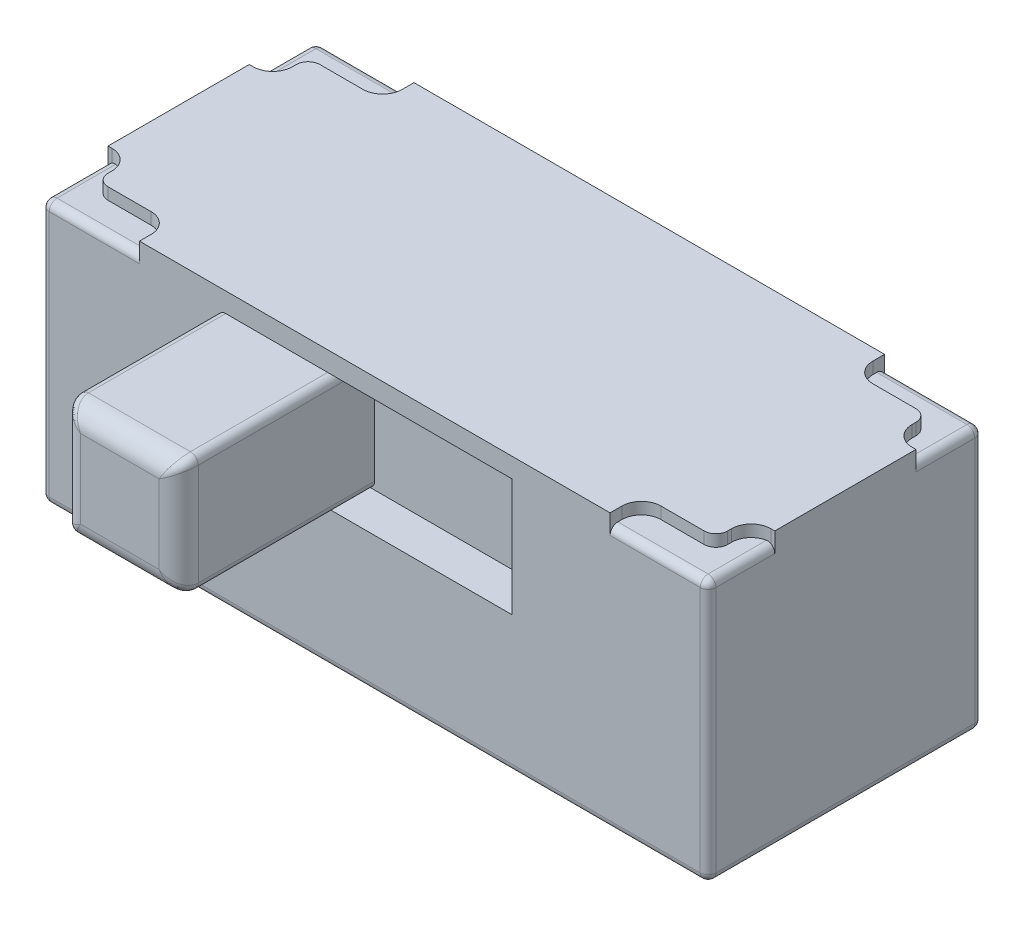
SolidWorks part; units mm, degrees
ref_plane "Front Plane" through (0, 0, 0) normal (0, 0, 1) x (1, 0, 0)
ref_plane "Top Plane" through (0, 0, 0) normal (0, 1, 0) x (1, 0, 0)
ref_plane "Right Plane" through (0, 0, 0) normal (1, 0, 0) x (0, 0, -1)
sketch "Sketch1" plane through (0, 0, 0) normal (0, 1, 0) x (1, 0, 0)
  line L1 (-4.25, -1.75) -> (4.25, -1.75)
  line L2 (-4.25, -1.75) -> (-4.25, 1.75)
  line L3 (-4.25, 1.75) -> (4.25, 1.75)
  line L4 (4.25, -1.75) -> (4.25, 1.75)
  line L5 (-4.25, -1.75) -> (4.25, 1.75) construction
  line L6 (-4.25, 1.75) -> (4.25, -1.75) construction
  point P0 (0, 0)
  dimension "D1" = 8.5
  dimension "D2" = 3.5
extrude "Bloc" add sketch "Sketch1" along normal blind 3.5
sketch "Sketch2" plane through (0, 0, 0) normal (1, 0, 0) x (0, 0, -1)
  line L0 (-2.1, 0) -> (-2.5, 0)
  line L1 (-1.75, 3.5) -> (-1.75, 0) construction
  line L2 (-1.75, 0.35) -> (-1.75, 0.75)
  line L3 (-1.75, 0) -> (1.75, 0) construction
  arc A0 (-1.75, 0.35) -> (-2.1, 0) centre (-2.1, 0.35) cw
  dimension "D1" = 0.4
  dimension "D2" = 2.5
extrude "Patte" add sketch "Sketch2" along normal mid plane 0.6 separate body thin thin type one direction reverse wall 0.25
pattern_linear "LPattern1" count 2 spacing 2.5 along (1, 0, 0) count 2 spacing 2.5 along (-1, 0, 0) of "Patte" pattern seed only yes
mirror "Mirror1" about plane through (0, 0, 0) normal (0, 0, 1) of "LPattern1", "Patte"
sketch "Sketch4" plane through (0, 0, 1.75) normal (0, 0, 1) x (1, 0, 0)
  line L0 (-1.75, 2.5) -> (1.75, 2.5) construction
  line L1 (-1.75, 3.25) -> (1.75, 3.25)
  line L2 (-1.75, 3.25) -> (-1.75, 1.75)
  line L3 (-1.75, 1.75) -> (1.75, 1.75)
  line L4 (1.75, 3.25) -> (1.75, 1.75)
  line L5 (-4.25, 0) -> (4.25, 0) construction
  line L6 (0, 3.25) -> (0, 1.75) construction
  line L7 (0, 1.75) -> (0, 0) construction
  line L8 (0.3, 0) -> (-0.3, 0) construction
  dimension "D1" = 2.5
  dimension "D2" = 3.5
  dimension "D3" = 1.5
extrude "Découpe switch" cut sketch "Sketch4" against normal blind 0.5
sketch "Sketch3" plane through (0, 0, 1.25) normal (0, 0, 1) x (1, 0, 0)
  line L0 (-4.25, 3.5) -> (4.25, 3.5) construction
  line L1 (-2, 3.25) -> (-0.5, 3.25)
  line L2 (-2, 3.25) -> (-2, 1.75)
  line L3 (-2, 1.75) -> (-0.5, 1.75)
  line L4 (-0.5, 3.25) -> (-0.5, 1.75)
  line L5 (0, 3.5) -> (0, 0) construction
  line L6 (-1.25, 1.75) -> (-1.25, 3.25) construction
  line L7 (-1.25, 2.5) -> (1.25, 2.5) construction
  line L8 (1.25, 3.5) -> (1.25, 0) construction
  line L9 (-4.25, 0) -> (4.25, 0) construction
  line L10 (-2, 2.5) -> (-0.5, 2.5) construction
  point P19 (0, 2.5)
  dimension "D1" = 1.5
  dimension "D2" = 1.5
  dimension "D3" = 2.5
  dimension "D4" = 2.5
extrude "Switch" add sketch "Sketch3" along normal offset from surface (2.5 mm away) 2 separate body up to face at (0, 2.5, 1.75) offset beyond the face yes
sketch "Sketch5" plane through (0, 3.5, 0) normal (0, 1, 0) x (1, 0, 0)
  line L0 (-4.25, 1.75) -> (-3, 1.75)
  line L1 (4.25, 1.75) -> (-4.25, 1.75) construction
  line L2 (-3, 1.75) -> (-3, 1.6)
  line L3 (-3.25, 1.35) -> (-3.8, 1.35)
  line L4 (-3.95, 1.2) -> (-3.95, 1.15)
  line L5 (-4.2, 0.9) -> (-4.25, 0.9)
  line L6 (-4.25, 1.75) -> (-4.25, -1.75) construction
  line L7 (-4.25, 0.9) -> (-4.25, 1.75)
  line L8 (-4.25, 0) -> (4.25, 0) construction
  line L9 (4.25, -1.75) -> (4.25, 1.75) construction
  line L10 (4.25, 0.9) -> (4.25, 1.75)
  line L11 (0.3, 1.75) -> (-0.3, 1.75) construction
  line L12 (0, 1.75) -> (0, -1.75) construction
  line L13 (-4.25, -1.75) -> (4.25, -1.75) construction
  line L14 (4.2, 0.9) -> (4.25, 0.9)
  line L15 (3.95, 1.2) -> (3.95, 1.15)
  line L16 (3.25, 1.35) -> (3.8, 1.35)
  line L17 (3, 1.75) -> (3, 1.6)
  line L18 (4.25, 1.75) -> (3, 1.75)
  line L19 (4.25, -1.75) -> (3, -1.75)
  line L20 (3, -1.75) -> (3, -1.6)
  line L21 (3.25, -1.35) -> (3.8, -1.35)
  line L22 (3.95, -1.2) -> (3.95, -1.15)
  line L23 (4.2, -0.9) -> (4.25, -0.9)
  line L24 (4.25, -0.9) -> (4.25, -1.75)
  line L25 (-4.25, -0.9) -> (-4.25, -1.75)
  line L26 (-4.2, -0.9) -> (-4.25, -0.9)
  line L27 (-3.95, -1.2) -> (-3.95, -1.15)
  line L28 (-3.25, -1.35) -> (-3.8, -1.35)
  line L29 (-3, -1.75) -> (-3, -1.6)
  line L30 (-4.25, -1.75) -> (-3, -1.75)
  arc A0 (-3, 1.6) -> (-3.25, 1.35) centre (-3.25, 1.6) cw
  arc A1 (-3.95, 1.15) -> (-4.2, 0.9) centre (-4.2, 1.15) cw
  arc A2 (-3.8, 1.35) -> (-3.95, 1.2) centre (-3.8, 1.2) ccw
  arc A3 (3.8, 1.35) -> (3.95, 1.2) centre (3.8, 1.2) cw
  arc A4 (3.95, 1.15) -> (4.2, 0.9) centre (4.2, 1.15) ccw
  arc A5 (3, 1.6) -> (3.25, 1.35) centre (3.25, 1.6) ccw
  arc A6 (3, -1.6) -> (3.25, -1.35) centre (3.25, -1.6) cw
  arc A7 (3.95, -1.15) -> (4.2, -0.9) centre (4.2, -1.15) cw
  arc A8 (3.8, -1.35) -> (3.95, -1.2) centre (3.8, -1.2) ccw
  arc A9 (-3.8, -1.35) -> (-3.95, -1.2) centre (-3.8, -1.2) cw
  arc A10 (-3.95, -1.15) -> (-4.2, -0.9) centre (-4.2, -1.15) ccw
  arc A11 (-3, -1.6) -> (-3.25, -1.35) centre (-3.25, -1.6) ccw
  point P23 (-3, 1.35)
  point P26 (-3.95, 0.9)
  point P41 (3.95, 0.9)
  point P42 (3, 1.35)
  point P55 (3, -1.35)
  point P56 (3.95, -0.9)
  point P69 (-3.95, -0.9)
  point P70 (-3, -1.35)
  dimension "D5" = 0.25
  dimension "D6" = 0.15
  dimension "D1" = 0.3
  dimension "D2" = 0.4
  dimension "D3" = 1.25
  dimension "D4" = 0.85
extrude "Cut-Extrude2" cut sketch "Sketch5" against normal blind 0.15
fillet "Fillet1" radius 0.1 16 edges at (0, 0, -1.75) (0, 0, 1.75) (-4.25, 1.675, -1.75) (-4.25, 1.675, 1.75) (-4.25, 0, 0) (4.25, 1.675, 1.75) (4.25, 1.675, -1.75) (4.25, 0, 0) (-4.25, 3.35, -1.325) (-4.25, 3.35, 1.325) (-3.625, 3.35, 1.75) (-3.625, 3.35, -1.75) (3.625, 3.35, -1.75) (4.25, 3.35, -1.325) (3.625, 3.35, 1.75) (4.25, 3.35, 1.325)
fillet "Fillet2" radius 0.25 4 edges at (-2, 2.5, 3.75) (-1.25, 3.25, 3.75) (-0.5, 2.5, 3.75) (-1.25, 1.75, 3.75)
fillet "Fillet3" radius 0.1 8 edges at (-1.9268, 1.8232, 3.6768) (-1.9268, 3.1768, 3.6768) (-0.5732, 1.8232, 3.6768) (-0.5732, 3.1768, 3.6768) (-2, 1.75, 2.375) (-2, 3.25, 2.375) (-0.5, 1.75, 2.375) (-0.5, 3.25, 2.375)
sketch "Sketch6" plane through (0, 0, 1.75) normal (0, 0, 1) x (1, 0, 0)
  line L1 (-3.5396, -0.9602) -> (3.5396, -0.9602)
  line L2 (-3.5396, -0.9602) -> (-3.5396, 0.9602)
  line L3 (-3.5396, 0.9602) -> (3.5396, 0.9602)
  line L4 (3.5396, -0.9602) -> (3.5396, 0.9602)
  line L5 (-3.5396, -0.9602) -> (3.5396, 0.9602) construction
  line L6 (-3.5396, 0.9602) -> (3.5396, -0.9602) construction
extrude "Cut-Extrude3" cut sketch "Sketch6" along normal blind 10
equation "\"D2@Sketch4\"=2+1.5"
